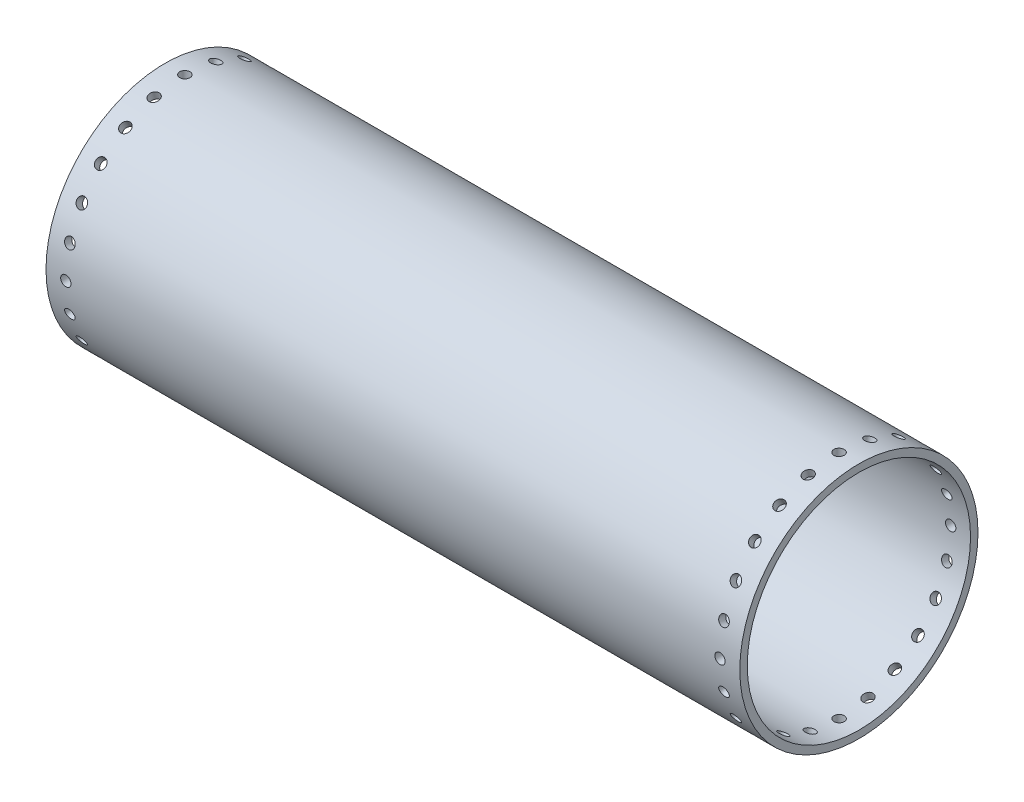
SolidWorks part; units mm, degrees
ref_plane "Front Plane" through (0, 0, 0) normal (0, 0, 1) x (1, 0, 0)
ref_plane "Top Plane" through (0, 0, 0) normal (0, 1, 0) x (1, 0, 0)
ref_plane "Right Plane" through (0, 0, 0) normal (1, 0, 0) x (0, 0, -1)
sketch "Tube Sketch" plane through (0, 0, 0) normal (0, 0, 1) x (1, 0, 0)
  line L0 (-1000, 0) -> (1000, 0) construction
  line L1 (0, 71.425) -> (443.9048, 71.425)
  line L2 (443.9048, 71.425) -> (443.9048, 76.2)
  line L3 (443.9048, 76.2) -> (0, 76.2)
  line L4 (0, 76.2) -> (0, 71.425)
revolve "Tube" add sketch "Tube Sketch" angle 360 about L0
ref_axis "Engine Axis" through (466.1001, 0, 0) along (-1, 0, 0)
ref_plane "Bottom End" through (443.9048, 0, 0) normal (1, 0, 0) x (0, 0, -1)
sketch "Top Screw Hole Sketch" plane through (0, 0, 0) normal (0, 0, 1) x (1, 0, 0)
  line L0 (12.7, 51.425) -> (12.7, 96.2) construction
  line L1 (12.7, 70.425) -> (16, 70.425)
  line L2 (16, 70.425) -> (16, 77.2)
  line L3 (16, 77.2) -> (12.7, 77.2)
  line L4 (12.7, 77.2) -> (12.7, 70.425)
revolve "Top Screw Hole" cut sketch "Top Screw Hole Sketch" angle 360 about L0
pattern_circular "Top Screw Holes x24" count 24 over 360 about axis through (466.1001, 0, 0) along (-1, 0, 0) of "Top Screw Hole"
sketch "Bottom Screw Hole Sketch" plane through (0, 0, 0) normal (0, 0, 1) x (1, 0, 0)
  line L0 (431.2048, 51.425) -> (431.2048, 96.2) construction
  line L1 (431.2048, 70.425) -> (434.5048, 70.425)
  line L2 (434.5048, 70.425) -> (434.5048, 77.2)
  line L3 (434.5048, 77.2) -> (431.2048, 77.2)
  line L4 (431.2048, 77.2) -> (431.2048, 70.425)
revolve "Bottom Screw Hole" cut sketch "Bottom Screw Hole Sketch" angle 360 about L0
pattern_circular "Bottom Screw Holes x24" count 24 over 360 about axis through (466.1001, 0, 0) along (-1, 0, 0) of "Bottom Screw Hole"
